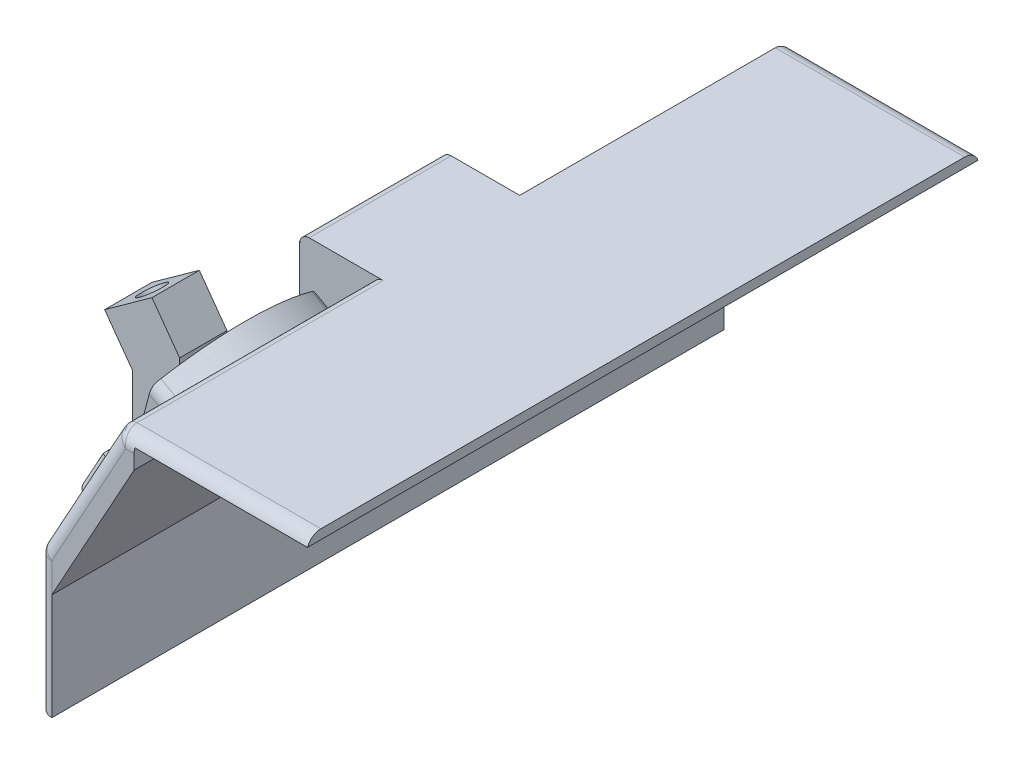
SolidWorks part; units mm, degrees
ref_plane "Front Plane" through (0, 0, 0) normal (0, 0, 1) x (1, 0, 0)
ref_plane "Top Plane" through (0, 0, 0) normal (0, 1, 0) x (1, 0, 0)
ref_plane "Right Plane" through (0, 0, 0) normal (1, 0, 0) x (0, 0, -1)
sketch "Sketch1" plane through (0, 0, 0) normal (0, 0, 1) x (1, 0, 0)
  line L0 (0, 0) -> (0, 29.4737)
  line L1 (0, 29.4737) -> (16.8421, 60)
  line L2 (16.8421, 60) -> (56.8421, 60)
  line L3 (56.8421, 60) -> (56.8421, 54)
  line L4 (56.8421, 54) -> (20.3844, 54)
  line L5 (20.3844, 54) -> (8.0932, 31.7223)
  line L6 (8.0932, 31.7223) -> (8.0932, 0)
  line L7 (8.0932, 0) -> (0, 0)
  dimension "D1" = 40
  dimension "D2" = 60
  dimension "D3" = 54
  dimension "D4" = 6
  dimension "D5" = 6
  dimension "D6" = 8.0932
extrude "Boss-Extrude1" add sketch "Sketch1" along normal blind 142
sketch "Sketch2" plane through (0, 0, 0) normal (0, -1, 0) x (1, 0, 0)
  line L0 (0, 142) -> (0, 0) construction
  line L1 (0, 112) -> (-10, 112)
  line L2 (0, 112) -> (0, 102)
  line L3 (0, 102) -> (-10, 102)
  line L4 (-10, 112) -> (-10, 102)
  dimension "D1" = 30
  dimension "D2" = 10
  dimension "D3" = 10
extrude "Boss-Extrude2" add sketch "Sketch2" against normal up to surface (60 mm away) up to face at (36.8421, 60, 71)
sketch "Sketch3" plane through (0, 0, 102) normal (0, 0, -1) x (-1, 0, 0)
  line L0 (0, 49.3327) -> (10, 42.1303)
  line L1 (0, 60) -> (0, 29.4737) construction
  line L2 (10, 60) -> (10, 0) construction
  line L3 (10, 42.1303) -> (10, 60)
  line L4 (10, 60) -> (0, 60)
  line L5 (0, 60) -> (0, 49.3327)
extrude "Cut-Extrude1" cut sketch "Sketch3" against normal up to surface (10 mm away) up to face at (-4, 29.8947, 112)
sketch "Sketch4" plane through (-23.3952, 32.4826, 0) normal (-0.5844, 0.8114, 0) x (0.8114, 0.5844, 0)
  line L4 (28.8316, -112) -> (28.8316, -102)
  line L5 (28.8316, -102) -> (16.5079, -102)
  line L6 (16.5079, -102) -> (16.5079, -112)
  line L7 (16.5079, -112) -> (28.8316, -112)
  line L8 (28.8316, -112) -> (28.8316, -102)
  line L9 (28.8316, -102) -> (16.5079, -102)
  line L10 (16.5079, -102) -> (16.5079, -112)
  line L11 (16.5079, -112) -> (28.8316, -112)
  dimension "D1" = 0
extrude "Boss-Extrude3" add sketch "Sketch4" along normal blind 10
sketch "Sketch5" plane through (-29.2395, 40.597, 0) normal (-0.5844, 0.8114, 0) x (0.8114, 0.5844, 0)
  line L0 (22.6697, -102) -> (22.6697, -112) construction
  line L3 (28.8316, -102) -> (16.5079, -102) construction
  line L4 (16.5079, -112) -> (28.8316, -112) construction
  line L5 (16.5079, -107) -> (28.8316, -107) construction
  line L6 (16.5079, -112) -> (16.5079, -102) construction
  line L7 (28.8316, -112) -> (28.8316, -102) construction
  circle A0 centre (22.6697, -107) radius 2.75
  dimension "D1" = 5.5
extrude "Cut-Extrude2" cut sketch "Sketch5" against normal blind 20
sketch "Sketch6" plane through (0, 60, 0) normal (0, 1, 0) x (1, 0, 0)
  line L0 (16.8421, -142) -> (16.8421, 0) construction
  line L1 (16.8421, -15) -> (6, -15)
  line L2 (16.8421, -15) -> (16.8421, -50)
  line L3 (16.8421, -50) -> (6, -50)
  line L4 (6, -15) -> (6, -50)
  line L5 (16.8421, 0) -> (0, 0) construction
  line L6 (0, -102) -> (0, 0) construction
  dimension "D1" = 35
  dimension "D2" = 15
  dimension "D3" = 6
extrude "Cut-Extrude3" cut sketch "Sketch6" against normal blind 15
sketch "Sketch7" plane through (0, 0, 15) normal (0, 0, 1) x (1, 0, 0)
  line L0 (16.8421, 49.6497) -> (14.2768, 45)
  line L4 (16.8421, 47.5796) -> (16.8421, 60)
  line L5 (16.8421, 60) -> (8.5662, 45)
  line L6 (8.5662, 45) -> (15.4189, 45)
  line L7 (15.4189, 45) -> (16.8421, 47.5796)
  line L8 (16.8421, 47.5796) -> (16.8421, 49.6497)
  line L10 (14.2768, 45) -> (15.4189, 45)
  line L11 (15.4189, 45) -> (16.8421, 47.5796)
  point P6 (16.1305, 46.2898)
  dimension "D2" = 1
  dimension "D1" = 0
extrude "Boss-Extrude4" add sketch "Sketch7" along normal up to surface (35 mm away) up to face at (14.4173, 49.3949, 50)
fillet "Fillet2" radius 3 1 edges at (0, 29.4737, 51)
fillet "Fillet3" radius 3 1 edges at (0, 29.4737, 127)
fillet "Fillet4" radius 3 8 edges at (0, 14.3505, 142) (0.0948, 29.4493, 142) (0, 14.3505, 0) (0.0948, 29.4493, 0) (8.6077, 45.0751, 142) (8.6077, 45.0751, 0) (36.8421, 60, 0) (36.8421, 60, 142)
sketch "Sketch8" plane through (0, 60, 0) normal (0, 1, 0) x (1, 0, 0)
  line L0 (0.3733, -3) -> (0.3733, -102) construction
  line L1 (0.3733, -57) -> (16.8421, -57)
  line L2 (0.3733, -57) -> (0.3733, -87)
  line L3 (0.3733, -87) -> (16.8421, -87)
  line L4 (16.8421, -57) -> (16.8421, -87)
  line L5 (16.8421, -139) -> (16.8421, -50) construction
  line L6 (-5.8443, -102) -> (0, -102) construction
  dimension "D1" = 30
  dimension "D2" = 15
extrude "Boss-Extrude5" add sketch "Sketch8" against normal up to surface (12.4204 mm away) up to face at (14.2388, 42.8612, 71)
fillet "Fillet6" radius 2 1 edges at (0.3733, 60, 72)
fillet "Fillet7" radius 2 2 edges at (17.3609, 59.1213, 141.1213) (16.8421, 60, 113)
sketch "Sketch9" plane through (-12.4665, 6.8781, 0) normal (-0.8756, 0.4831, 0) x (0, 0, 1)
  line L0 (87, 59.4899) -> (87, 26.5792) construction
  line L1 (92, 53.5564) -> (127, 53.5564)
  line L2 (92, 53.5564) -> (92, 33.5564)
  line L3 (92, 33.5564) -> (127, 33.5564)
  line L4 (127, 53.5564) -> (127, 33.5564)
  dimension "D1" = 35
  dimension "D2" = 20
  dimension "D3" = 5
extrude "Cut-Extrude4" cut sketch "Sketch9" against normal blind 3
sketch "Sketch11" plane through (-12.4665, 6.8781, 0) normal (-0.8756, 0.4831, 0) x (0, 0, 1)
  line L0 (127, 53.5564) -> (92, 53.5564) construction
  line L1 (127, 53.5564) -> (122.8121, 53.5564)
  line L4 (96.1879, 53.5564) -> (92, 53.5564)
  arc A0 (92, 53.5564) -> (127, 53.5564) centre (109.5, 25.273) cw
  arc A1 (96.1879, 53.5564) -> (122.8121, 53.5564) centre (109.5, 25.273) cw
  arc A3 (93.0523, 51.8557) -> (125.9477, 51.8557) centre (109.5, 25.273) cw construction
  dimension "D1" = 2
extrude "Boss-Extrude6" add sketch "Sketch11" along normal blind 5
sketch "Sketch12" plane through (0.3733, 0, 0) normal (-1, 0, 0) x (0, 0, 1)
  line L0 (87, 30.1502) -> (87, 58) construction
  line L1 (64.5, 55.873) -> (80.5, 55.873)
  line L2 (64.5, 55.873) -> (64.5, 53.873)
  line L3 (64.5, 53.873) -> (80.5, 53.873)
  line L4 (80.5, 55.873) -> (80.5, 53.873)
  line L5 (57.5, 57.873) -> (86.5, 57.873)
  line L6 (57.5, 57.873) -> (57.5, 49.873)
  line L7 (57.5, 49.873) -> (86.5, 49.873)
  line L8 (86.5, 57.873) -> (86.5, 49.873)
  line L9 (57, 30.1502) -> (57, 60) construction
  line L10 (58, 57.373) -> (86, 57.373)
  line L11 (86, 57.373) -> (86, 50.373)
  line L12 (58, 50.373) -> (86, 50.373)
  line L13 (58, 57.373) -> (58, 50.373)
  dimension "D1" = 2
  dimension "D2" = 16
  dimension "D3" = 8
  dimension "D4" = 0.5
  dimension "D5" = 0.5
  dimension "D6" = 2
  dimension "D7" = 7
  dimension "D8" = 0.5
extrude "Boss-Extrude7" add sketch "Sketch12" along normal blind 0.5 contours L8 L5 L6 L7 L13 L10 L11 L12 | L4 L1 L2 L3 region at (0.3733, 54.873, 72.5) region at (0.3733, 57.5722, 72)
sketch "Sketch13" plane through (0.3733, 0, 0) normal (-1, 0, 0) x (0, 0, 1)
  line L0 (64.5, 53.873) -> (80.5, 53.873) construction
  line L1 (66, 53.373) -> (79, 53.373)
  line L2 (66, 53.373) -> (66, 50.873)
  line L3 (66, 50.873) -> (79, 50.873)
  line L4 (79, 53.373) -> (79, 50.873)
  dimension "D1" = 0.5
  dimension "D2" = 1.5
  dimension "D3" = 1.5
  dimension "D4" = 2.5
extrude "Cut-Extrude5" cut sketch "Sketch13" against normal blind 0.5
sketch "Sketch14" plane through (0.3733, 0, 0) normal (-1, 0, 0) x (0, 0, 1)
  line L0 (58, 57.373) -> (58, 50.373) construction
  line L1 (86, 57.373) -> (86, 50.373) construction
  line L2 (58, 57.373) -> (86, 57.373) construction
  circle A0 centre (61, 54.873) radius 1.25
  circle A1 centre (83, 54.873) radius 1.25
  dimension "D2" = 2.5
  dimension "D4" = 2.5
  dimension "D1" = 3
  dimension "D3" = 3
  dimension "D5" = 2.5
  dimension "D6" = 2.5
extrude "Boss-Extrude8" add sketch "Sketch14" along normal blind 1.5
sketch "Sketch15" plane through (-12.4665, 6.8781, 0) normal (-0.8756, 0.4831, 0) x (0, 0, 1)
  line L0 (139, 26.5792) -> (139, 59.4899) construction
  line L1 (130, 48.2564) -> (138, 48.2564)
  line L2 (130, 48.2564) -> (130, 38.2564)
  line L3 (130, 38.2564) -> (138, 38.2564)
  line L4 (138, 48.2564) -> (138, 38.2564)
  point P6 (139, 43.0346)
  dimension "D1" = 10
  dimension "D2" = 8
  dimension "D3" = 1
extrude "Boss-Extrude9" add sketch "Sketch15" along normal blind 1.5
fillet "Fillet9" radius 1 4 edges at (4.7009, 41.0992, 134) (7.1163, 45.477, 138) (7.1163, 45.477, 130) (9.5317, 49.8549, 134)
sketch "Sketch17" plane through (-9.8398, 5.4289, 0) normal (-0.8756, 0.4831, 0) x (0, 0, 1)
  line L0 (92, 53.5564) -> (92, 33.5564) construction
  line L1 (92, 53.5564) -> (92, 33.5564)
  line L2 (94, 53.5564) -> (94, 33.5564)
  line L3 (92, 53.5564) -> (94, 53.5564)
  line L4 (92, 33.5564) -> (94, 33.5564)
  line L5 (127, 33.5564) -> (127, 53.5564) construction
  line L6 (127, 33.5564) -> (127, 53.5564)
  line L7 (125, 33.5564) -> (125, 53.5564)
  line L8 (127, 33.5564) -> (125, 33.5564)
  line L9 (127, 53.5564) -> (125, 53.5564)
  dimension "D1" = 2
  dimension "D2" = 2
extrude "Boss-Extrude10" add sketch "Sketch17" along normal up to surface (8 mm away) up to face at (9.9879, 57.927, 109.5)
sketch "Sketch18" plane through (0, 0, 127) normal (0, 0, 1) x (1, 0, 0)
  line L0 (3.7438, 36.2594) -> (9.0275, 56.1863)
  line L1 (9.0275, 56.1863) -> (-0.6341, 38.6748)
  line L2 (-0.6341, 38.6748) -> (3.7438, 36.2594)
extrude "Cut-Extrude6" cut sketch "Sketch18" against normal up to surface (35 mm away) up to face at (6.3857, 46.2228, 92)
fillet "Fillet10" radius 3 1 edges at (11.2164, 54.9786, 127)
fillet "Fillet11" radius 3 1 edges at (11.2164, 54.9786, 92)
sketch "Sketch19" plane through (0, 0, 142) normal (0, 0, 1) x (1, 0, 0)
  line L6 (56.8421, 57) -> (56.8421, 60) construction
  line L7 (20.3844, 54) -> (56.8421, 54)
  line L8 (20.3844, 54) -> (20.3844, 58)
  line L9 (20.3844, 58) -> (56.8421, 58)
  line L10 (56.8421, 54) -> (56.8421, 58)
  dimension "D1" = 4
extrude "Cut-Extrude7" cut sketch "Sketch19" against normal up to surface (142 mm away) up to face at (21.8585, 35.3029, 0)
sketch "Sketch20" plane through (0, 0, 142) normal (0, 0, 1) x (1, 0, 0)
  line L0 (8.0932, 31.7223) -> (5.5965, 27.197)
  line L1 (18.6132, 57) -> (3, 28.701) construction
  line L2 (5.5965, 27.197) -> (3, 22.4908)
  line L3 (3, 28.701) -> (3, 0) construction
  line L4 (3, 22.4908) -> (3, 0)
  line L5 (3, 0) -> (8.0932, 0)
  line L6 (8.0932, 0) -> (8.0932, 31.7223)
extrude "Cut-Extrude8" cut sketch "Sketch20" against normal up to surface (142 mm away) up to face at (11.6526, 32.6319, 0)
sketch "Sketch21" plane through (-9.8398, 5.4289, 0) normal (-0.8756, 0.4831, 0) x (0, 0, 1)
  line L1 (116.9818, 50.5713) -> (118.4818, 50.5713)
  line L2 (116.9818, 50.5713) -> (116.9818, 47.5713)
  line L3 (116.9818, 47.5713) -> (118.4818, 47.5713)
  line L4 (118.4818, 50.5713) -> (118.4818, 47.5713)
  line L5 (119.0818, 50.5713) -> (120.5818, 50.5713)
  line L6 (119.0818, 50.5713) -> (119.0818, 47.5713)
  line L7 (119.0818, 47.5713) -> (120.5818, 47.5713)
  line L8 (120.5818, 50.5713) -> (120.5818, 47.5713)
  line L9 (121.1818, 50.5713) -> (122.6818, 50.5713)
  line L10 (121.1818, 50.5713) -> (121.1818, 47.5713)
  line L11 (121.1818, 47.5713) -> (122.6818, 47.5713)
  line L12 (122.6818, 50.5713) -> (122.6818, 47.5713)
  line L13 (116.9818, 46.7713) -> (118.4818, 46.7713)
  line L14 (116.9818, 46.7713) -> (116.9818, 43.7329)
  line L15 (116.9818, 43.7329) -> (118.4818, 43.7329)
  line L16 (118.4818, 46.7713) -> (118.4818, 43.7329)
  line L17 (119.0818, 46.7713) -> (120.5818, 46.7713)
  line L18 (119.0818, 46.7713) -> (119.0818, 43.7329)
  line L19 (119.0818, 43.7329) -> (120.5818, 43.7329)
  line L20 (120.5818, 46.7713) -> (120.5818, 43.7329)
  line L21 (121.1818, 46.7713) -> (122.6818, 46.7713)
  line L22 (121.1818, 46.7713) -> (121.1818, 43.7329)
  line L23 (121.1818, 43.7329) -> (122.6818, 43.7329)
  line L24 (122.6818, 46.7713) -> (122.6818, 43.7329)
  dimension "D1" = 3
  dimension "D2" = 1.5
  dimension "D3" = 0.6
  dimension "D4" = 0.6
  dimension "D5" = 1.5
  dimension "D6" = 1.5
  dimension "D7" = 0.8
  dimension "D8" = 0.6
  dimension "D9" = 1.5
  dimension "D10" = 1.5
  dimension "D11" = 0.6
  dimension "D12" = 1.5
  dimension "D13" = 0.8
extrude "Boss-Extrude11" add sketch "Sketch21" along normal blind 0.5
sketch "Sketch22" plane through (-9.8398, 5.4289, 0) normal (-0.8756, 0.4831, 0) x (0, 0, 1)
  line L0 (100.0453, 46.6091) -> (102.0453, 42.0714)
  line L1 (102.0453, 42.0714) -> (112.0782, 42.0714)
  line L2 (112.0782, 42.0714) -> (114.0782, 46.6091)
  line L3 (102, 36.3392) -> (112, 36.3392) construction
  line L5 (94, 33.5564) -> (125, 33.5564) construction
  line L6 (94, 33.5564) -> (125, 33.5564) construction
  arc A0 (100.0453, 46.6091) -> (114.0782, 46.6091) centre (107.0617, 42.0714) cw
  circle A1 centre (96.846, 43.3344) radius 2.5
  circle A2 centre (115.3082, 42.0714) radius 1.5
  circle A3 centre (96.846, 36.5564) radius 2
  circle A4 centre (102.5998, 36.5564) radius 2
  circle A5 centre (109.004, 36.3392) radius 2
  circle A6 centre (115.3082, 36.3392) radius 2
  dimension "D3" = 5
  dimension "D4" = 3
  dimension "D5" = 4
  dimension "D6" = 4
  dimension "D7" = 4
  dimension "D8" = 4
  dimension "D1" = 2
  dimension "D2" = 2
  dimension "D9" = 3
  dimension "D10" = 3
  dimension "D11" = 2.7827
extrude "Boss-Extrude12" add sketch "Sketch22" along normal blind 0.5
sketch "Sketch23" plane through (0.3733, 0, 0) normal (-1, 0, 0) x (0, 0, 1)
  line L0 (66.1074, 41.3565) -> (76.1074, 41.3565)
  line L1 (66.1325, 40.8565) -> (76.0824, 40.8565)
  arc A0 (66.1325, 40.8565) -> (76.0824, 40.8565) centre (71.1074, 41.3565) ccw
  circle A1 centre (71.1074, 41.3565) radius 5.5
  arc A2 (76.1074, 41.3565) -> (66.1074, 41.3565) centre (71.1074, 41.3565) ccw
  circle A3 centre (71.1074, 41.3565) radius 5 construction
  point P8 (75.8889, 42.8184)
  dimension "D1" = 10
  dimension "D3" = 0.5
  dimension "D2" = 0.5
extrude "Boss-Extrude13" add sketch "Sketch23" along normal blind 0.5
